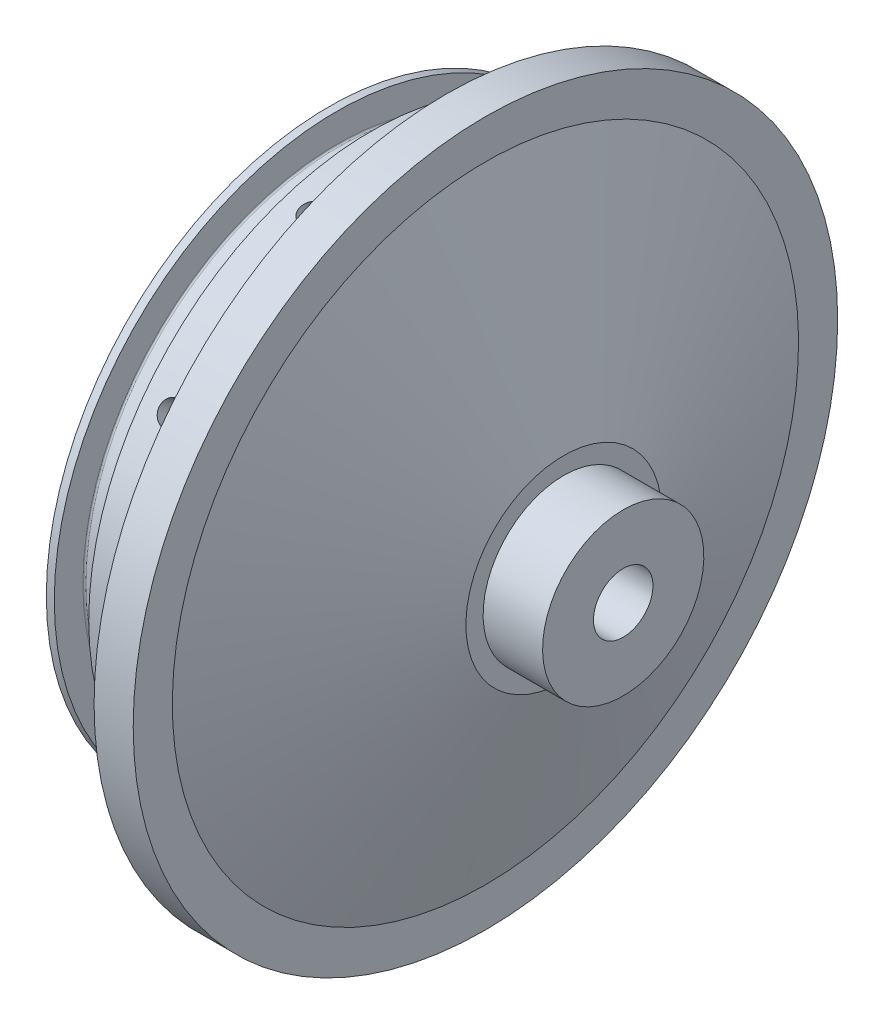
SolidWorks part; units mm, degrees
material "7075-T6 (SN)"
ref_plane "Front Plane" through (0, 0, 0) normal (0, 0, 1) x (1, 0, 0)
ref_plane "Top Plane" through (0, 0, 0) normal (0, 1, 0) x (1, 0, 0)
ref_plane "Right Plane" through (0, 0, 0) normal (1, 0, 0) x (0, 0, -1)
sketch "Sketch1" plane through (0, 0, 0) normal (1, 0, 0) x (0, 0, -1)
  circle A0 centre (0, 0) radius 57.15
  dimension "D1" = 114.3
extrude "Boss-Extrude1" add sketch "Sketch1" along normal blind 6.35
sketch "Sketch2" plane through (0, 0, 0) normal (-1, 0, 0) x (0, 0, 1)
  circle A0 centre (0, 0) radius 45.847
  dimension "D1" = 91.694
extrude "Boss-Extrude2" add sketch "Sketch2" along normal blind 19.05
sketch "Sketch3" plane through (-19.05, 0, 0) normal (-1, 0, 0) x (0, 0, 1)
  circle A0 centre (0, 0) radius 38.227
  dimension "D1" = 76.454
extrude "Cut-Extrude1" cut sketch "Sketch3" against normal blind 6.604
sketch "Sketch5" plane through (0, 0, 0) normal (0, 0, 1) x (1, 0, 0)
  line L0 (6.35, -50.8) -> (19.05, -15.875)
  line L1 (6.35, -57.15) -> (6.35, 57.15) construction
  line L2 (6.35, 0) -> (19.05, 0)
  line L3 (19.05, 0) -> (19.05, -15.875)
  line L4 (6.35, -50.8) -> (6.35, 0)
  dimension "D1" = 50.8
  dimension "D2" = 15.875
  dimension "D3" = 12.7
revolve "Revolve1" add sketch "Sketch5" angle 360 about L2
sketch "Sketch6" plane through (19.05, 0, 0) normal (1, 0, 0) x (0, 0, -1)
  circle A0 centre (0, 0) radius 13.081
  dimension "D1" = 26.162
extrude "Boss-Extrude3" add sketch "Sketch6" along normal blind 9.652
sketch "Sketch7" plane through (28.702, 0, 0) normal (1, 0, 0) x (0, 0, -1)
  circle A0 centre (0, 0) radius 4.826
  dimension "D1" = 9.652
extrude "Cut-Extrude2" cut sketch "Sketch7" against normal through all
sketch "Sketch8" plane through (0, 0, 0) normal (0, 0, 1) x (1, 0, 0)
  line L0 (0, 0) -> (-12.446, 0)
  line L1 (-12.446, 38.227) -> (-12.446, -38.227) construction
  line L2 (-12.446, 0) -> (-12.446, -29.21)
  line L4 (10.414, 0) -> (0, 0)
  line L6 (10.414, -15.875) -> (10.414, 0)
  line L7 (-12.446, -29.21) -> (-2.794, -29.21)
  line L8 (-2.794, -29.21) -> (10.414, -15.875)
  dimension "D1" = 29.21
  dimension "D2" = 12.446
  dimension "D3" = 15.875
  dimension "D4" = 10.414
  dimension "D5" = 9.652
revolve "Cut-Revolve2" cut sketch "Sketch8" angle 360 about L4
fillet "Fillet1" radius 2.032 2 edges at (-2.794, 29.21, 0) (10.414, 15.875, 0)
sketch "Sketch10" plane through (0, 0, 0) normal (0, 1, 0) x (1, 0, 0)
  line L0 (0, 0) -> (-53.2238, 0) construction
  line L1 (-26.2636, 0) -> (26.2636, 0) construction
  line L2 (0, 0) -> (0, 64.5447) construction
  line L3 (0, -62.865) -> (0, 62.865) construction
ref_plane "Plane1" through (0, 0, -45.847) normal (0, 0, -1) x (-1, 0, 0)
sketch "Sketch11" plane through (0, 0, -45.847) normal (0, 0, -1) x (-1, 0, 0)
  line L0 (0, 0) -> (53.2238, 0) construction
  line L1 (0, -45.847) -> (0, 45.847) construction
  circle A0 centre (7.62, 0) radius 1.8986
  dimension "D2" = 3.7973
  dimension "D1" = 7.62
extrude "Cut-Extrude3" cut sketch "Sketch11" against normal blind 11.43
pattern_circular "CirPattern1" count 10 every 36 about axis through (0, 0, 0) along (-1, 0, 0) of "Cut-Extrude3" reverse direction yes
sketch "Sketch13" plane through (0, 0, 0) normal (0, 0, 1) x (1, 0, 0)
  line L0 (-19.05, 0) -> (-19.05, 45.847) construction
  line L1 (-19.05, 38.227) -> (-19.05, -38.227) construction
  line L2 (-19.05, 45.847) -> (0, 45.847) construction
  line L3 (0, 45.847) -> (0, -45.847) construction
  line L4 (0, 0) -> (-64.5609, 0) construction
  line L5 (-17.7575, 45.847) -> (-12.1695, 45.847)
  line L6 (-17.7575, 45.847) -> (-17.7575, 41.2115)
  line L7 (-17.5035, 40.9575) -> (-12.4235, 40.9575)
  line L8 (-12.1695, 45.847) -> (-12.1695, 41.2115)
  arc A0 (-12.4235, 40.9575) -> (-12.1695, 41.2115) centre (-12.4235, 41.2115) ccw
  arc A1 (-17.5035, 40.9575) -> (-17.7575, 41.2115) centre (-17.5035, 41.2115) cw
  point P13 (-12.1695, 40.9575)
  point P16 (-17.7575, 40.9575)
  dimension "D4" = 0.254
  dimension "D1" = 45.847
  dimension "D2" = 5.588
  dimension "D3" = 40.9575
revolve "Cut-Revolve3" cut sketch "Sketch13" angle 360 about L4
sketch "Sketch14" plane through (-12.446, 0, 0) normal (-1, 0, 0) x (0, 0, 1)
  line L0 (0, 0) -> (0, 33.3375) construction
  circle A0 centre (0, 33.3375) radius 1.1303
  dimension "D2" = 2.2606
  dimension "D1" = 33.3375
extrude "Cut-Extrude4" cut sketch "Sketch14" against normal blind 6.35
pattern_circular "CirPattern2" count 8 every 45 about axis through (-12.446, 0, 0) along (1, 0, 0) of "Cut-Extrude4"
